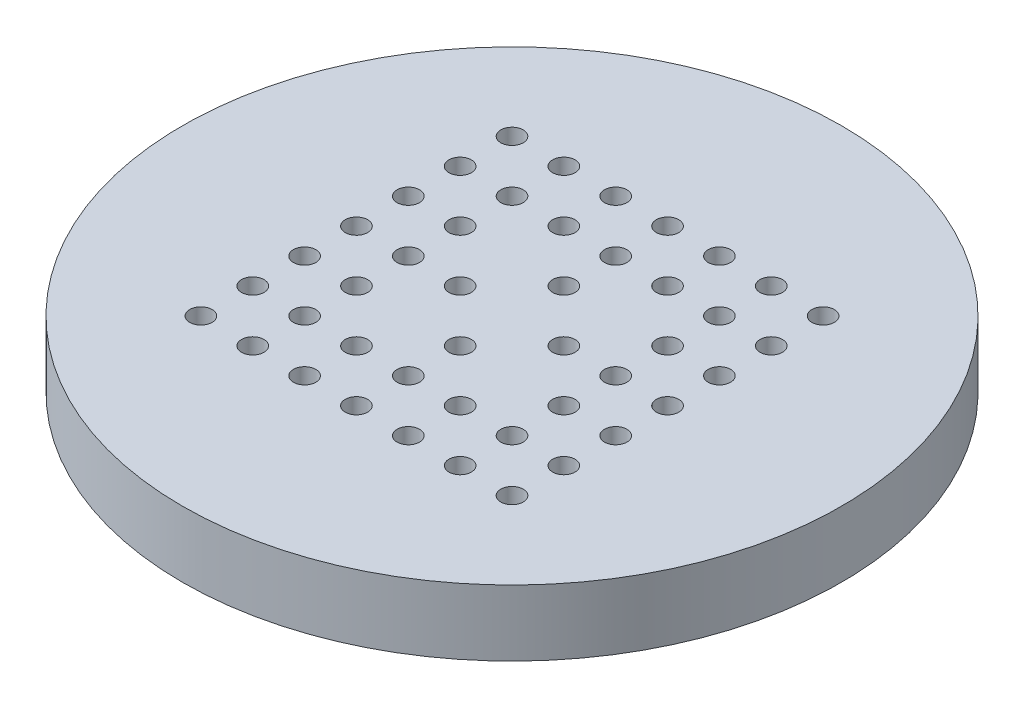
SolidWorks part; units mm, degrees
ref_plane "Front Plane" through (0, 0, 0) normal (0, 0, 1) x (1, 0, 0)
ref_plane "Top Plane" through (0, 0, 0) normal (0, 1, 0) x (1, 0, 0)
ref_plane "Right Plane" through (0, 0, 0) normal (1, 0, 0) x (0, 0, -1)
ref_axis "Axial" through (0, -55, 0) along (0, 1, 0)
ref_plane "Bottom Plane" through (0, -3.81, 0) normal (0, 1, 0) x (1, 0, 0)
sketch "Sketch1" plane through (0, 0, 0) normal (0, 1, 0) x (1, 0, 0)
  circle A0 centre (0, 0) radius 19.05
  dimension "D1" = 38.1
extrude "Billet" add sketch "Sketch1" against normal blind 3.81
sketch "Sketch2" plane through (0, 0, 0) normal (0, 1, 0) x (1, 0, 0)
  line L0 (0, 18.6449) -> (0, -20.0163) construction
  line L1 (-17.698, 0) -> (15.8694, 0) construction
  circle A0 centre (8.9916, 8.9916) radius 0.6477
  dimension "D1" = 1.2954
  dimension "D2" = 8.9916
  dimension "D3" = 8.9916
extrude "First Lox Hole" cut sketch "Sketch2" against normal through all and the other way through all contours A0
chamfer "Braising Chamfer" distance 0.254 angle 45 1 edges at (8.9916, -3.81, -8.3439)
pattern_linear "Lox Hole Pattern" count 7 spacing 2.9972 along (-1, 0, 0) count 7 spacing 2.9972 along (0, 0, 1) skipping (2, 2), (2, 4), (3, 3), (4, 2), (4, 4) of "First Lox Hole", "Braising Chamfer"
sketch "Sketch3" plane through (0, -3.81, 0) normal (0, 1, 0) x (-1, 0, 0)
  line L0 (0, 21.0611) -> (0, -20.7325) construction
  line L1 (-20.4368, 0) -> (21.7511, 0) construction
  circle A3 centre (0, 15.24) radius 0.7937
  circle A4 centre (0, -15.24) radius 0.7937
  dimension "D4" = 15.24
  dimension "D3" = 1.5875
extrude "Dowel Hole" cut sketch "Sketch3" along normal blind 1.905
